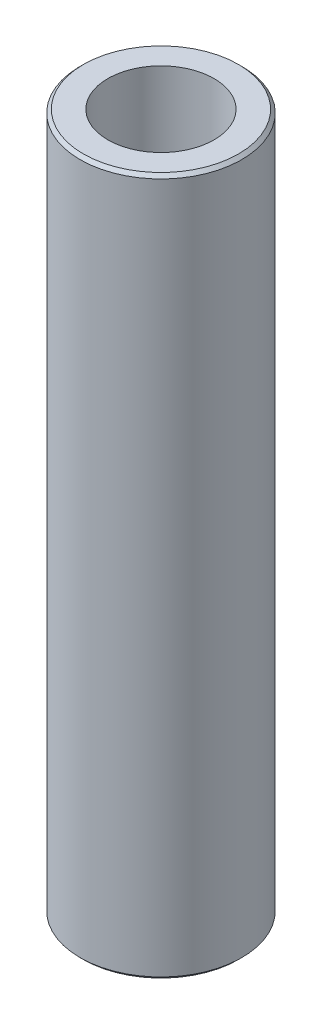
SolidWorks part; units mm, degrees
ref_plane "Front Plane" through (0, 0, 0) normal (0, 0, 1) x (1, 0, 0)
ref_plane "Top Plane" through (0, 0, 0) normal (0, 1, 0) x (1, 0, 0)
ref_plane "Right Plane" through (0, 0, 0) normal (1, 0, 0) x (0, 0, -1)
sketch "Sketch1" plane through (0, 0, 0) normal (0, 1, 0) x (1, 0, 0)
  circle A0 centre (0, 0) radius 15
  dimension "SHAFT_OD" = 30
extrude "Boss-Extrude1" add sketch "Sketch1" along normal blind 129.4673
sketch "Sketch2" plane through (0, 0, 0) normal (0, 1, 0) x (1, 0, 0)
  circle A0 centre (0, 0) radius 9.8605
  dimension "BORE_D" = 19.7209
extrude "Cut-Extrude1" cut sketch "Sketch2" along normal through all
chamfer "Chamfer1" distance 0.6079 angle 45 2 edges at (0, 129.4673, 15) (0, 0, 15)
